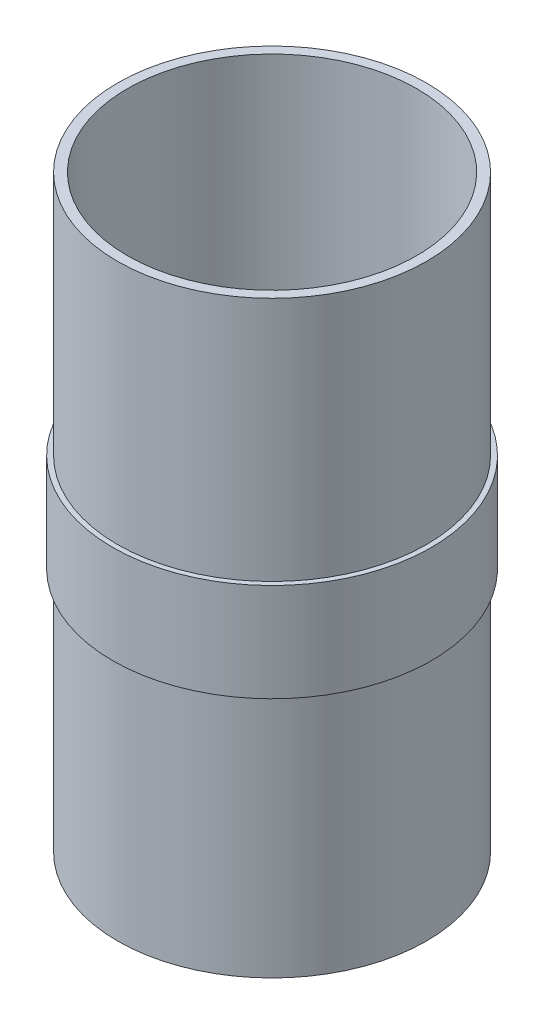
SolidWorks part; units mm, degrees
other "Marcação1"
sketch "Esboço5" plane through (-34.5, 110, -34.5) normal (-0.0418, 0.9983, -0.0408) x (0.9924, 0.0462, 0.1144)
material "Plástico personalizado (1)"
ref_plane "Plano frontal" through (0, 0, 0) normal (0, 0, 1) x (1, 0, 0)
ref_plane "Plano superior" through (0, 0, 0) normal (0, 1, 0) x (1, 0, 0)
ref_plane "Plano direito" through (0, 0, 0) normal (1, 0, 0) x (0, 0, -1)
sketch "Esboço1" plane through (0, 0, 0) normal (0, 1, 0) x (1, 0, 0)
  circle A0 centre (0, 0) radius 31.5
  circle A1 centre (0, 0) radius 29.5
extrude "Ressalto-extrusão1" add sketch "Esboço1" along normal blind 50 contours A1 | A0
sketch "Esboço2" plane through (0, 50, 0) normal (0, 1, 0) x (1, 0, 0)
  circle A0 centre (0, 0) radius 32.5
  circle A1 centre (0, 0) radius 29.5
extrude "Ressalto-extrusão2" add sketch "Esboço2" along normal blind 20 separate body contours A1 | A0
sketch "Esboço3" plane through (0, 70, 0) normal (0, 1, 0) x (1, 0, 0)
  circle A0 centre (0, 0) radius 29.5
  circle A1 centre (0, 0) radius 31.5
extrude "Ressalto-extrusão3" add sketch "Esboço3" along normal blind 50 separate body contours A1 | A0
sketch "Esboço6" plane through (0, 70, 0) normal (0, 1, 0) x (1, 0, 0)
  circle A0 centre (0, 0) radius 30.5
extrude "Ressalto-extrusão4" add sketch "Esboço6" against normal blind 5
combine bodies "Combinar3" operation type add bodies to combine 101 115
